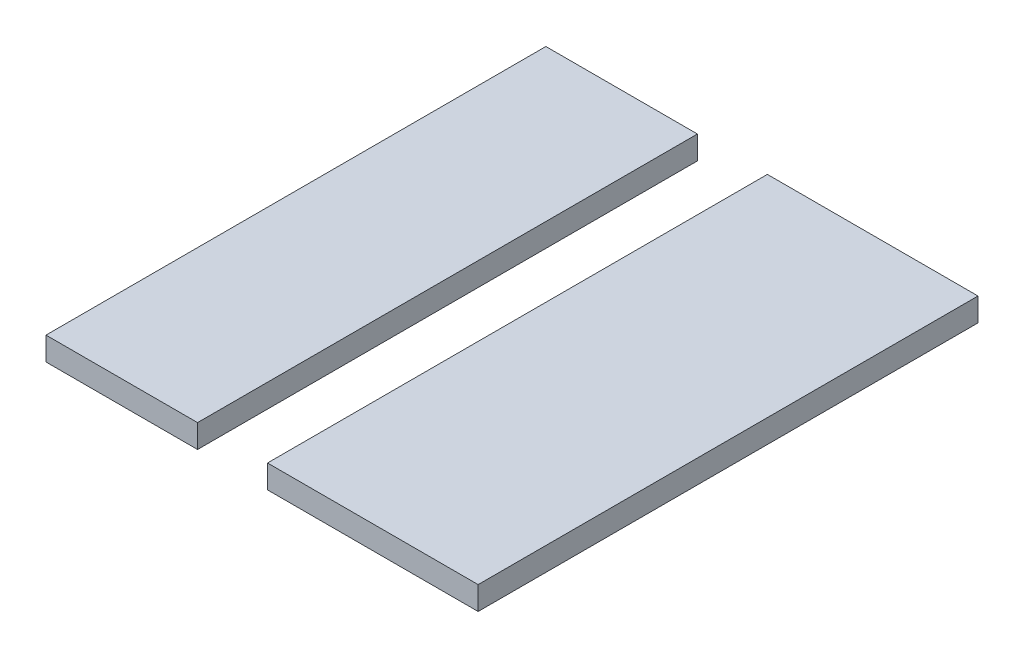
SolidWorks part; units mm, degrees
ref_plane "Front Plane" through (0, 0, 0) normal (0, 0, 1) x (1, 0, 0)
ref_plane "Top Plane" through (0, 0, 0) normal (0, 1, 0) x (1, 0, 0)
ref_plane "Right Plane" through (0, 0, 0) normal (1, 0, 0) x (0, 0, -1)
sketch "Sketch1" plane through (0, 0, 0) normal (0, 1, 0) x (1, 0, 0)
  line L0 (0.7, -32.157) -> (0.7, 32.157)
  line L1 (-28.5, -32.157) -> (28.5, -32.157) construction
  line L2 (-28.5, -32.157) -> (-28.5, 32.157) construction
  line L3 (-28.5, 32.157) -> (28.5, 32.157) construction
  line L4 (28.5, -32.157) -> (28.5, 32.157) construction
  line L5 (-8.3, 32.157) -> (-8.3, -32.157)
  line L6 (27.8, -32.157) -> (27.8, 32.157)
  line L7 (-27.8, -32.157) -> (-27.8, 32.157)
  line L8 (0, -32.157) -> (0, 32.157) construction
  line L9 (0.7, -32.157) -> (27.8, -32.157)
  line L10 (27.8, 32.157) -> (0.7, 32.157)
  line L11 (-8.3, 32.157) -> (-27.8, 32.157)
  line L12 (-8.3, -32.157) -> (-27.8, -32.157)
  line L13 (28.5, 0) -> (27.8, 0) construction
  line L14 (27.8, 20) -> (28.5, 20) construction
sketch "Sketch2" plane through (0, 0, 0) normal (0, 0, 1) x (1, 0, 0)
  line L0 (0.7, 0) -> (27.8, 0) construction
  line L1 (27.8, 0) -> (0.7, 0)
  line L2 (27.8, 0) -> (27.8, 3)
  line L3 (27.8, 3) -> (0.7, 3)
  line L4 (0.7, 0) -> (0.7, 3)
  line L5 (28.5, 3) -> (0.7, 3) construction
  line L7 (-8.3, 3) -> (-27.8, 3)
  line L8 (-8.3, 3) -> (-8.3, 0)
  line L9 (-8.3, 0) -> (-27.8, 0)
  line L10 (-27.8, 3) -> (-27.8, 0)
extrude "Boss-Extrude1" add sketch "Sketch1" along normal up to vertex (3 mm away) up to point (-27.8, 3, 0)
